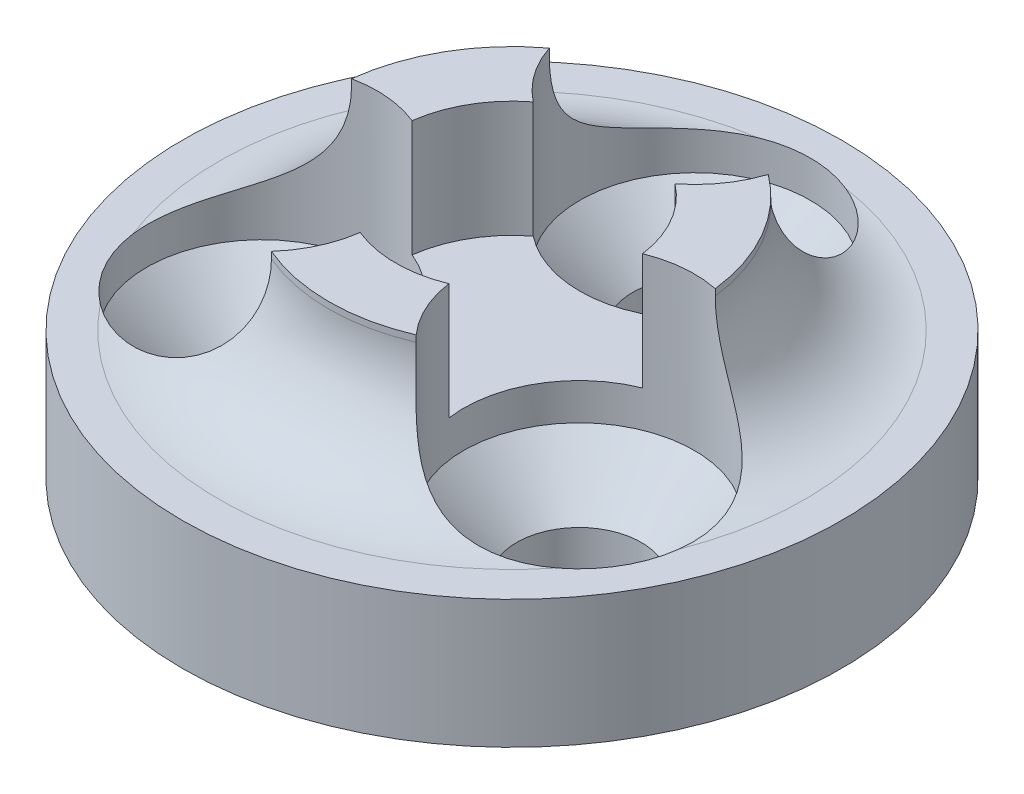
SolidWorks part; units mm, degrees
ref_plane "Front Plane" through (0, 0, 0) normal (0, 0, 1) x (1, 0, 0)
ref_plane "Top Plane" through (0, 0, 0) normal (0, 1, 0) x (1, 0, 0)
ref_plane "Right Plane" through (0, 0, 0) normal (1, 0, 0) x (0, 0, -1)
sketch "Sketch1" plane through (0, 0, 0) normal (0, 1, 0) x (1, 0, 0)
  circle A0 centre (0, 0) radius 9
  dimension "D1" = 18
extrude "Boss-Extrude1" add sketch "Sketch1" along normal blind 3.5
sketch "Sketch2" plane through (0, 3.5, 0) normal (0, 1, 0) x (1, 0, 0)
  line L0 (0, 0) -> (0, 5) construction
  line L2 (4.3301, -2.5) -> (0, 0) construction
  line L3 (-4.3301, -2.5) -> (0, 0) construction
  circle A0 centre (0, 0) radius 5 construction
  dimension "D3" = 10
  dimension "D1" = 120
  dimension "D2" = 120
hole_wizard "CSK for M3 Flat Head Machine Screw1" positions "Sketch4" profile "Sketch3" countersink size "M3" standard "ANSI Metric"
sketch "Sketch4" plane through (0, 3.5, 0) normal (0, 1, 0) x (1, 0, 0)
  point P0 (0, 5)
  point P3 (4.3301, -2.5)
  point P5 (-4.3301, -2.5)
sketch "Sketch3" plane through (0, 3.5, -5) normal (1, 0, 0) x (0, 0, 1)
  line L0 (0, 0) -> (0, 11.0215)
  line L1 (0, 11.0215) -> (1.7, 10)
  line L2 (1.7, 10) -> (1.7, 2.45)
  line L3 (1.7, 2.45) -> (3.15, 1)
  line L4 (3.15, 1) -> (3.15, 0)
  line L6 (3.15, 0) -> (0, 0)
  line L7 (-1.7, 2.45) -> (-3.15, 1) construction
  line L10 (0, 11.0215) -> (-1.7, 10) construction
  line L11 (0, -6.35) -> (0, 107.95) construction
  dimension "Hole Dia." = 3.4
  dimension "Hole Depth" = 10
  dimension "C'Sink Dia." = 6.3
  dimension "C'Sink Angle" = 90
  dimension "Drill Angle" = 118
  dimension "Head Clearance" = 1
sketch "Sketch5" plane through (0, 3.5, 0) normal (0, 1, 0) x (1, 0, 0)
  arc A0 (-1.9368, 2.5158) -> (-3.1472, 0.4194) centre (0, 0) ccw
  arc A1 (-2.9896, 4.0077) -> (-1.9368, 2.5158) centre (0, 5) ccw
  arc A2 (4.9656, 0.5852) -> (3.1472, 0.4194) centre (4.3301, -2.5) ccw
  arc A3 (-1.976, -4.593) -> (-1.2103, -2.9353) centre (-4.3301, -2.5) ccw
  arc A4 (-2.9896, 4.0077) -> (-4.9656, 0.5852) centre (0, 0) ccw
  arc A5 (-1.976, -4.593) -> (1.976, -4.593) centre (0, 0) ccw
  arc A6 (-1.2103, -2.9353) -> (1.2103, -2.9353) centre (0, 0) ccw
  arc A7 (4.9656, 0.5852) -> (2.9896, 4.0077) centre (0, 0) ccw
  arc A8 (3.1472, 0.4194) -> (1.9368, 2.5158) centre (0, 0) ccw
  arc A9 (-3.1472, 0.4194) -> (-4.9656, 0.5852) centre (-4.3301, -2.5) ccw
  arc A10 (1.2103, -2.9353) -> (1.976, -4.593) centre (4.3301, -2.5) ccw
  arc A11 (1.9368, 2.5158) -> (2.9896, 4.0077) centre (0, 5) ccw
  circle A13 centre (0, 5) radius 3.15 construction
  circle A14 centre (-4.3301, -2.5) radius 3.15 construction
  circle A15 centre (4.3301, -2.5) radius 3.15 construction
  dimension "D1" = 6.35
  dimension "D2" = 10
extrude "Boss-Extrude2" add sketch "Sketch5" along normal blind 3.175
fillet "Fillet1" radius 3 3 edges at (0, 3.5, 5) (4.3301, 3.5, -2.5)
sketch "Sketch6" plane through (0, 0, 0) normal (0, -1, 0) x (1, 0, 0)
  circle A0 centre (0, 0) radius 2.5
  dimension "D1" = 5
extrude "Boss-Extrude3" add sketch "Sketch6" along normal blind 3
